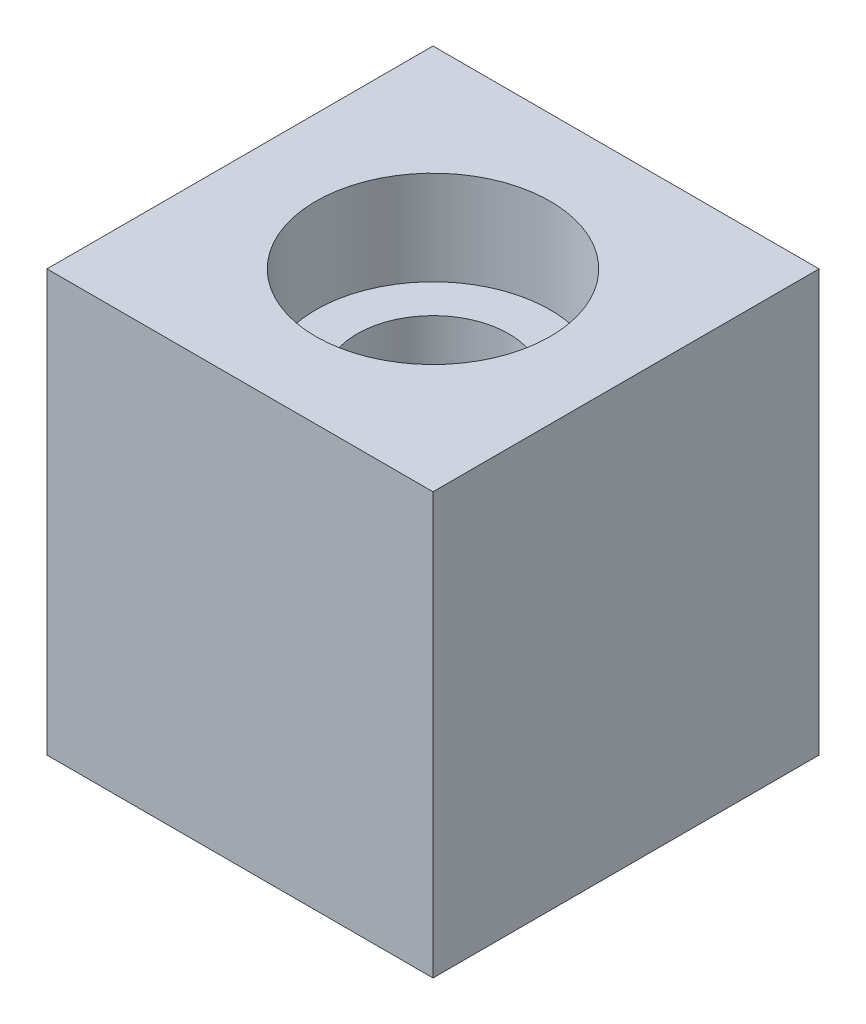
SolidWorks part; units mm, degrees
ref_plane "Front Plane" through (0, 0, 0) normal (0, 0, 1) x (1, 0, 0)
ref_plane "Top Plane" through (0, 0, 0) normal (0, 1, 0) x (1, 0, 0)
ref_plane "Right Plane" through (0, 0, 0) normal (1, 0, 0) x (0, 0, -1)
sketch "Sketch1" plane through (0, 0, 0) normal (0, 1, 0) x (1, 0, 0)
  line L1 (0, 0) -> (69.85, 0)
  line L2 (0, 0) -> (0, 69.85)
  line L3 (0, 69.85) -> (69.85, 69.85)
  line L4 (69.85, 0) -> (69.85, 69.85)
  dimension "D1" = 69.85
  dimension "D2" = 69.85
extrude "Boss-Extrude1" add sketch "Sketch1" along normal blind 76.2
sketch "Sketch2" plane through (0, 76.2, 0) normal (0, 1, 0) x (1, 0, 0)
  line L0 (69.85, 69.85) -> (0, 69.85) construction
  line L1 (34.925, 69.85) -> (34.925, 0) construction
  line L2 (0, 0) -> (69.85, 0) construction
  circle A0 centre (34.925, 34.925) radius 13.716
  dimension "D1" = 27.432
extrude "Cut-Extrude1" cut sketch "Sketch2" against normal blind 76.2
sketch "Sketch4" plane through (0, 76.2, 0) normal (0, 1, 0) x (1, 0, 0)
  line L0 (34.925, 69.85) -> (34.925, 0) construction
  line L1 (69.85, 69.85) -> (0, 69.85) construction
  line L2 (0, 0) -> (69.85, 0) construction
  circle A0 centre (34.925, 34.925) radius 21.209
  dimension "D1" = 42.418
extrude "Cut-Extrude2" cut sketch "Sketch4" against normal blind 17.018
sketch "Sketch5" plane through (0, 0, 0) normal (0, -1, 0) x (1, 0, 0)
  line L0 (69.85, -34.925) -> (0, -34.925) construction
  line L1 (69.85, 0) -> (69.85, -69.85) construction
  line L2 (0, -69.85) -> (0, 0) construction
  circle A0 centre (34.925, -34.925) radius 21.209
  dimension "D1" = 42.418
extrude "Cut-Extrude3" cut sketch "Sketch5" against normal blind 7.62 contours A0
